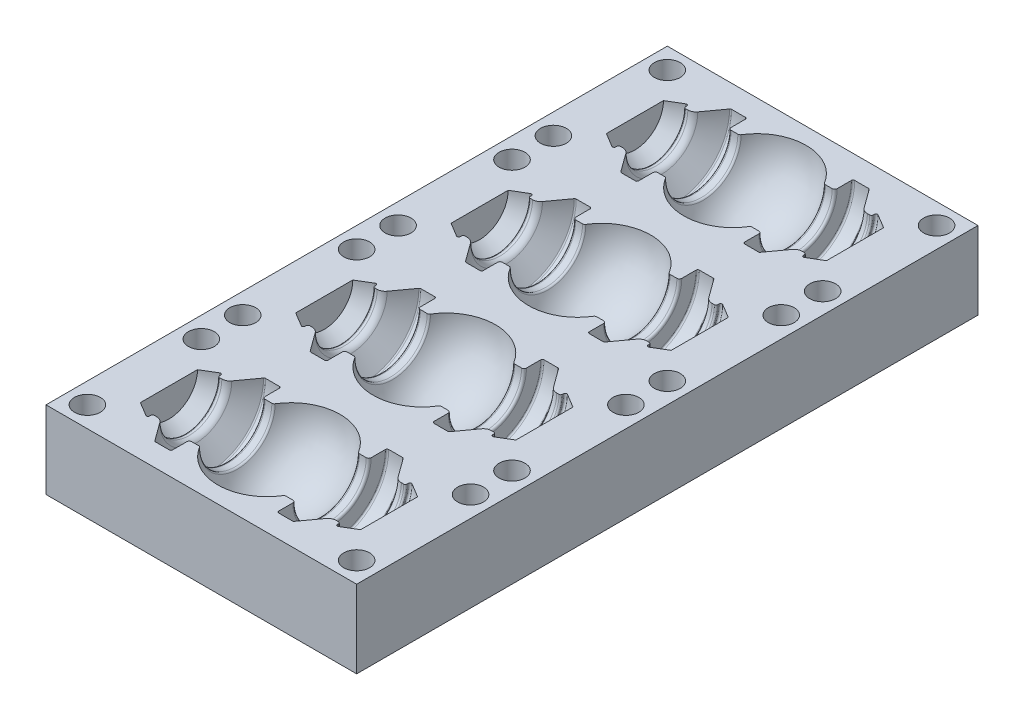
SolidWorks part; units mm, degrees
ref_plane "Front Plane" through (0, 0, 0) normal (0, 0, 1) x (1, 0, 0)
ref_plane "Top Plane" through (0, 0, 0) normal (0, 1, 0) x (1, 0, 0)
ref_plane "Right Plane" through (0, 0, 0) normal (1, 0, 0) x (0, 0, -1)
ref_axis "X - Axis" through (-88.99, 0, 0) along (1, 0, 0)
ref_axis "Y - Axis" through (0, 55, 0) along (0, -1, 0)
ref_axis "Z - Axis" through (0, 0, -88.99) along (0, 0, 1)
sketch "Sketch1" plane through (0, 0, 0) normal (0, 1, 0) x (1, 0, 0)
  line L1 (-19.05, 9.525) -> (19.05, 9.525)
  line L2 (-19.05, 9.525) -> (-19.05, -9.525)
  line L3 (-19.05, -9.525) -> (19.05, -9.525)
  line L4 (19.05, 9.525) -> (19.05, -9.525)
  line L5 (-19.05, 9.525) -> (19.05, -9.525) construction
  line L6 (-19.05, -9.525) -> (19.05, 9.525) construction
  point P0 (0, 0)
  dimension "D1" = 19.05
  dimension "D2" = 38.1
extrude "Boss-Extrude1" add sketch "Sketch1" against normal blind 9.525
sketch "Sketch2" plane through (0, 0, 0) normal (0, 1, 0) x (1, 0, 0)
  line L0 (-5.3703, 4.5) -> (-6.2, 4.5)
  line L1 (-6.7, 6.75) -> (-8.3982, 6.75)
  line L2 (-6.5, 4.8) -> (-6.5, 6.55)
  line L3 (-8.5599, 6.6676) -> (-10.2005, 4.4118)
  line L4 (-11.0092, 4) -> (-11.3, 4)
  line L5 (-11.5, 4.2) -> (-11.5, 4.3468)
  line L6 (-11.8029, 4.5183) -> (-13.5, 3.5)
  line L7 (0, 0) -> (0, 7.5) construction
  line L8 (-13.5, 0) -> (-13.5, 3.5)
  line L9 (-13.5, 0) -> (13.5, 0) construction
  line L10 (13.5, 3.5) -> (13.5, 0)
  line L11 (11.8029, 4.5183) -> (13.5, 3.5)
  line L12 (11.5, 4.2) -> (11.5, 4.3468)
  line L13 (11.0092, 4) -> (11.3, 4)
  line L14 (8.5599, 6.6676) -> (10.2005, 4.4118)
  line L15 (6.5, 4.8) -> (6.5, 6.55)
  line L16 (6.7, 6.75) -> (8.3982, 6.75)
  line L17 (5.3703, 4.5) -> (6.2, 4.5)
  line L18 (19.05, -9.525) -> (19.05, 9.525) construction
  line L19 (19.05, 9.525) -> (-19.05, 9.525) construction
  line L20 (-13.5, 0) -> (13.5, 0)
  arc A0 (5.1148, 4.6427) -> (-5.1148, 4.6427) centre (0, 1.4933) ccw
  arc A1 (-5.3703, 4.5) -> (-5.1148, 4.6427) centre (-5.3703, 4.8) ccw
  arc A2 (-6.5, 4.8) -> (-6.2, 4.5) centre (-6.2, 4.8) ccw
  arc A3 (-6.5, 6.55) -> (-6.7, 6.75) centre (-6.7, 6.55) ccw
  arc A4 (-8.3982, 6.75) -> (-8.5599, 6.6676) centre (-8.3982, 6.55) ccw
  arc A5 (-11.0092, 4) -> (-10.2005, 4.4118) centre (-11.0092, 5) ccw
  arc A6 (-11.5, 4.2) -> (-11.3, 4) centre (-11.3, 4.2) ccw
  arc A7 (-11.5, 4.3468) -> (-11.8029, 4.5183) centre (-11.7, 4.3468) ccw
  arc A8 (11.5, 4.3468) -> (11.8029, 4.5183) centre (11.7, 4.3468) cw
  arc A9 (11.5, 4.2) -> (11.3, 4) centre (11.3, 4.2) cw
  arc A10 (11.0092, 4) -> (10.2005, 4.4118) centre (11.0092, 5) cw
  arc A11 (8.3982, 6.75) -> (8.5599, 6.6676) centre (8.3982, 6.55) cw
  arc A12 (6.5, 6.55) -> (6.7, 6.75) centre (6.7, 6.55) cw
  arc A13 (6.5, 4.8) -> (6.2, 4.5) centre (6.2, 4.8) cw
  arc A14 (5.3703, 4.5) -> (5.1148, 4.6427) centre (5.3703, 4.8) cw
  point P93 (13.5, 0)
  dimension "D1" = 6.0067
  dimension "D2" = 0.3
  dimension "D3" = 0.2
  dimension "D4" = 1
  dimension "D5" = 5.55
  dimension "D6" = 7.2471
  dimension "D7" = 7.35
  dimension "D8" = 8.0408
  dimension "D9" = 8.8495
  dimension "D10" = 10.4901
  dimension "D11" = 12.55
  dimension "D12" = 13.6797
  dimension "D13" = 2.775
  dimension "D14" = 4.8823
  dimension "D15" = 5.0067
revolve "Cut-Revolve1" cut sketch "Sketch2" angle 360 about L20
hole_wizard "1/8 (0.125) Diameter Hole1" positions "Sketch7" profile "Sketch6" hole size "1/8" standard "ANSI Inch"
sketch "Sketch7" plane through (0, 0, 0) normal (0, 1, 0) x (1, 0, 0)
  line L1 (-16.51, 6.985) -> (16.51, 6.985)
  line L2 (-16.51, 6.985) -> (-16.51, -6.985)
  line L3 (-16.51, -6.985) -> (16.51, -6.985)
  line L4 (16.51, 6.985) -> (16.51, -6.985)
  line L5 (-16.51, 6.985) -> (16.51, -6.985) construction
  line L6 (-16.51, -6.985) -> (16.51, 6.985) construction
  line L7 (19.05, 9.525) -> (-19.05, 9.525) construction
  line L8 (-19.05, 9.525) -> (-19.05, -9.525) construction
  point P0 (-16.51, 6.985)
  point P2 (16.51, -6.985)
  point P4 (16.51, 6.985)
  point P6 (-16.51, -6.985)
  point P70 (0, 0)
  dimension "D1" = 2.54
  dimension "D2" = 2.54
sketch "Sketch6" plane through (-16.51, 0, -6.985) normal (1, 0, 0) x (0, 0, 1)
  line L0 (0, 0) -> (0, 7.3039)
  line L1 (0, 7.3039) -> (1.5875, 6.35)
  line L2 (1.5875, 6.35) -> (1.5875, 0)
  line L5 (1.5875, 0) -> (0, 0)
  line L10 (0, 7.3039) -> (-1.5875, 6.35) construction
  line L11 (0, -6.35) -> (0, 107.95) construction
  dimension "Hole Dia." = 3.175
  dimension "Hole Depth" = 6.35
  dimension "Drill Angle" = 118
sketch "Sketch8" plane through (-19.05, 0, 0) normal (-1, 0, 0) x (0, 0, 1)
  line L0 (-9.525, 0) -> (9.525, 0) construction
  circle A0 centre (0, 0) radius 1.5875
  dimension "D1" = 3.175
extrude "Cut-Extrude1" [suppressed] cut sketch "Sketch8" against normal through all
pattern_linear "LPattern1" [suppressed] count 4 spacing 19.05 of bodies 106
pattern_linear "LPattern2" count 4 spacing 19.05 along (0, 0, 1) of "1/8 (0.125) Diameter Hole1", "Cut-Revolve1", "Boss-Extrude1"
